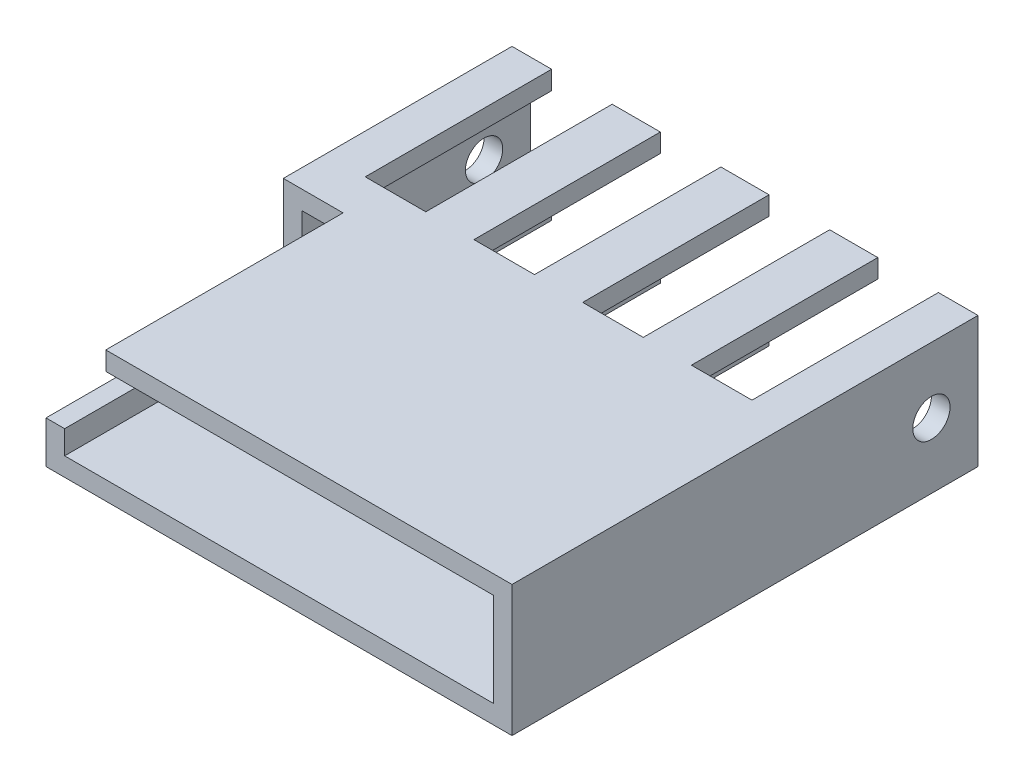
SolidWorks part; units mm, degrees
ref_plane "Front Plane" through (0, 0, 0) normal (0, 0, 1) x (1, 0, 0)
ref_plane "Top Plane" through (0, 0, 0) normal (0, 1, 0) x (1, 0, 0)
ref_plane "Right Plane" through (0, 0, 0) normal (1, 0, 0) x (0, 0, -1)
sketch "Sketch1" plane through (0, 0, 0) normal (0, 1, 0) x (1, 0, 0)
  line L1 (0, 0) -> (100, 0)
  line L2 (0, 0) -> (0, 100)
  line L3 (0, 100) -> (100, 100)
  line L4 (100, 0) -> (100, 100)
  dimension "D1" = 100
  dimension "D2" = 100
extrude "Boss-Extrude1" add sketch "Sketch1" along normal blind 28.1 contours L1 L4 L3 L2
shell "Shell1" thickness 4 removed face at (50, 14.05, -100) removed face at (50, 14.05, 0)
sketch "Sketch4" plane through (0, 0, 0) normal (0, -1, 0) x (1, 0, 0)
  line L1 (0, 0) -> (12.827, 0)
  line L2 (0, 0) -> (0, -50.927)
  line L3 (0, -50.927) -> (12.827, -50.927)
  line L4 (12.827, 0) -> (12.827, -50.927)
  dimension "D1" = 50.927
  dimension "D2" = 12.827
extrude "Cut-Extrude3" cut sketch "Sketch4" against normal through all from offset 9.05 offset against normal yes
sketch "Sketch5" plane through (0, 28.1, 0) normal (0, 1, 0) x (1, 0, 0)
  line L17 (100, 0) -> (100, 100) construction
  line L23 (0, 50.927) -> (0, 100) construction
  line L24 (21.5, 100) -> (8.5, 100)
  line L25 (21.5, 100) -> (21.5, 60)
  line L26 (21.5, 60) -> (8.5, 60)
  line L27 (8.5, 100) -> (8.5, 60)
  line L28 (21.5, 100) -> (8.5, 60) construction
  line L29 (21.5, 60) -> (8.5, 100) construction
  line L30 (44.8333, 100) -> (31.8333, 100)
  line L31 (44.8333, 100) -> (44.8333, 60)
  line L32 (44.8333, 60) -> (31.8333, 60)
  line L33 (31.8333, 100) -> (31.8333, 60)
  line L34 (44.8333, 100) -> (31.8333, 60) construction
  line L35 (44.8333, 60) -> (31.8333, 100) construction
  line L36 (68.1667, 100) -> (55.1667, 100)
  line L37 (68.1667, 100) -> (68.1667, 60)
  line L38 (68.1667, 60) -> (55.1667, 60)
  line L39 (55.1667, 100) -> (55.1667, 60)
  line L40 (68.1667, 100) -> (55.1667, 60) construction
  line L41 (68.1667, 60) -> (55.1667, 100) construction
  line L42 (91.5, 100) -> (78.5, 100)
  line L43 (91.5, 100) -> (91.5, 60)
  line L44 (91.5, 60) -> (78.5, 60)
  line L45 (78.5, 100) -> (78.5, 60)
  line L46 (91.5, 100) -> (78.5, 60) construction
  line L47 (91.5, 60) -> (78.5, 100) construction
  line L48 (15, 80) -> (85, 80) construction
  line L49 (0, 100) -> (100, 100) construction
  point P6 (15, 80)
  point P7 (38.3333, 80)
  point P8 (61.6667, 80)
  point P9 (85, 80)
  point P10 (38.3333, 80)
  point P11 (61.6667, 80)
  point P12 (15, 80)
  point P17 (38.3333, 80)
  point P22 (61.6667, 80)
  point P27 (85, 80)
  dimension "D1" = 15
  dimension "D2" = 13
  dimension "D4" = 15
  dimension "D3" = 40
extrude "Cut-Extrude4" cut sketch "Sketch5" against normal through all
sketch "Sketch6" plane through (0, 0, 0) normal (-1, 0, 0) x (0, 0, 1)
  line L0 (-100, 28.1) -> (-100, 0) construction
  circle A0 centre (-90, 14.05) radius 4
  point P6 (-100, 14.05)
  dimension "D1" = 8
  dimension "0.25" = 10
extrude "Cut-Extrude5" cut sketch "Sketch6" against normal through all and the other way blind 4.2672
